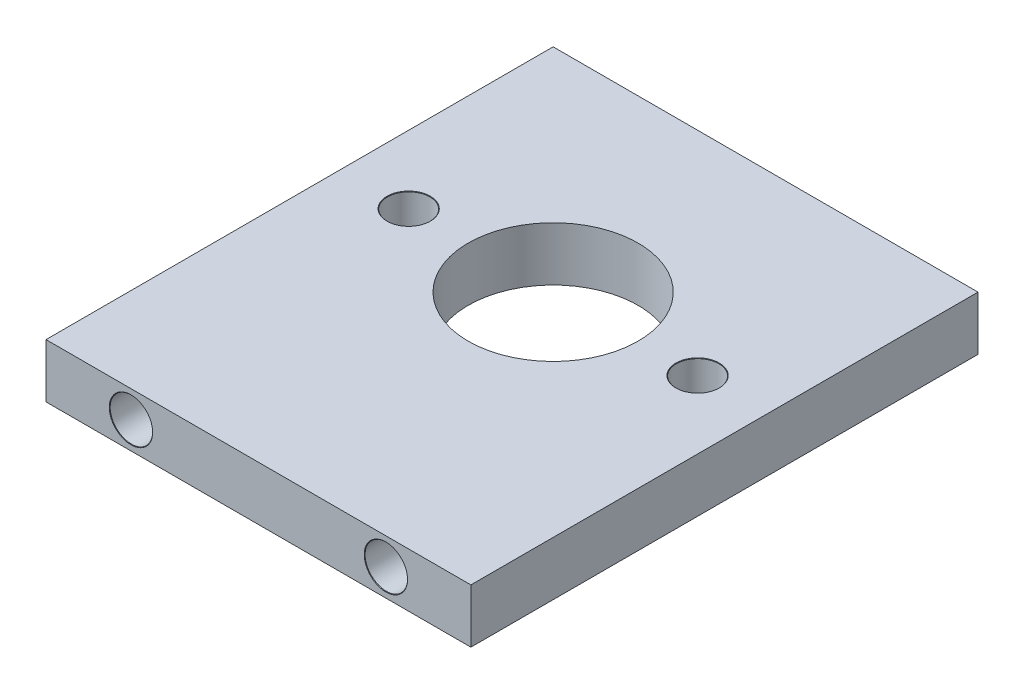
SolidWorks part; units mm, degrees
ref_plane "Front Plane" through (0, 0, 0) normal (0, 0, 1) x (1, 0, 0)
ref_plane "Top Plane" through (0, 0, 0) normal (0, 1, 0) x (1, 0, 0)
ref_plane "Right Plane" through (0, 0, 0) normal (1, 0, 0) x (0, 0, -1)
sketch "Sketch1" plane through (0, 0, 0) normal (0, 1, 0) x (1, 0, 0)
  line L0 (-12.5, -12.5) -> (-12.5, -17.34)
  line L1 (12.5, -12.5) -> (-12.5, -12.5) construction
  line L2 (12.5, -12.5) -> (12.5, 12.5)
  line L3 (12.5, 12.5) -> (-12.5, 12.5)
  line L4 (-12.5, -12.5) -> (-12.5, 12.5)
  line L5 (12.5, -12.5) -> (-12.5, 12.5) construction
  line L6 (12.5, 12.5) -> (-12.5, -12.5) construction
  line L7 (-12.5, -17.34) -> (12.5, -17.34)
  line L8 (12.5, -17.34) -> (12.5, -12.5)
  circle A0 centre (0, 0) radius 12.5 construction
  point P0 (0, 0)
  dimension "D1" = 25
  dimension "D2" = 17.34
extrude "Boss-Extrude1" add sketch "Sketch1" along normal blind 3.175
sketch "Sketch2" plane through (0, 3.175, 0) normal (0, 1, 0) x (1, 0, 0)
  line L0 (-8.5, 0) -> (8.5, 0) construction
  point P0 (-8.5, 0)
  point P1 (8.5, 0)
  point P2 (0, 0)
  dimension "D1" = 17
hole_wizard "Tap Drill for M3x0.5 Tap1" positions "Sketch2" profile "Sketch4" hole size "M3x0.5" standard "ANSI Metric" end condition through all
sketch "Sketch4" plane through (-8.5, 3.175, 0) normal (1, 0, 0) x (0, 0, 1)
  line L0 (0, 0) -> (0, 3.175)
  line L1 (0, 3.175) -> (1.25, 3.175)
  line L2 (1.25, 3.175) -> (1.25, 0.025)
  line L3 (1.25, 0.025) -> (1.275, 0)
  line L5 (1.275, 0) -> (0, 0)
  line L6 (-1.25, 0.025) -> (-1.275, 0) construction
  line L11 (0, -6.35) -> (0, 107.95) construction
  dimension "Thru Hole Dia." = 2.5
  dimension "Thru Hole Depth" = 3.175
  dimension "Near C'Sink Dia." = 2.55
  dimension "Near C'Sink Angle" = 90
hole_wizard "Tap Drill for M3x0.5 Tap2" positions "Sketch7" profile "Sketch6" hole size "M3x0.5" standard "ANSI Metric"
sketch "Sketch7" plane through (0, 0, 17.34) normal (0, 0, 1) x (1, 0, 0)
  line L0 (-7.5, 1.5875) -> (7.5, 1.5875) construction
  line L2 (-12.5, 3.175) -> (12.5, 3.175) construction
  line L3 (-12.5, 0) -> (12.5, 0) construction
  point P0 (-7.5, 1.5875)
  point P2 (7.5, 1.5875)
  point P10 (0, 1.5875)
  dimension "D1" = 15
sketch "Sketch6" plane through (-7.5, 1.5875, 17.34) normal (1, 0, 0) x (0, -1, 0)
  line L0 (0, 0) -> (0, 12.7511)
  line L1 (0, 12.7511) -> (1.25, 12)
  line L2 (1.25, 12) -> (1.25, 0.025)
  line L3 (1.25, 0.025) -> (1.275, 0)
  line L5 (1.275, 0) -> (0, 0)
  line L6 (-1.25, 0.025) -> (-1.275, 0) construction
  line L10 (0, 12.7511) -> (-1.25, 12) construction
  line L11 (0, -6.35) -> (0, 107.95) construction
  dimension "Hole Dia." = 2.5
  dimension "Hole Depth" = 12
  dimension "Near C'Sink Dia." = 2.55
  dimension "Near C'Sink Angle" = 90
  dimension "Drill Angle" = 118
sketch "Sketch8" plane through (0, 3.175, 0) normal (0, 1, 0) x (1, 0, 0)
  circle A0 centre (0, 0) radius 5
  dimension "D1" = 10
extrude "Cut-Extrude1" cut sketch "Sketch8" against normal up to next
